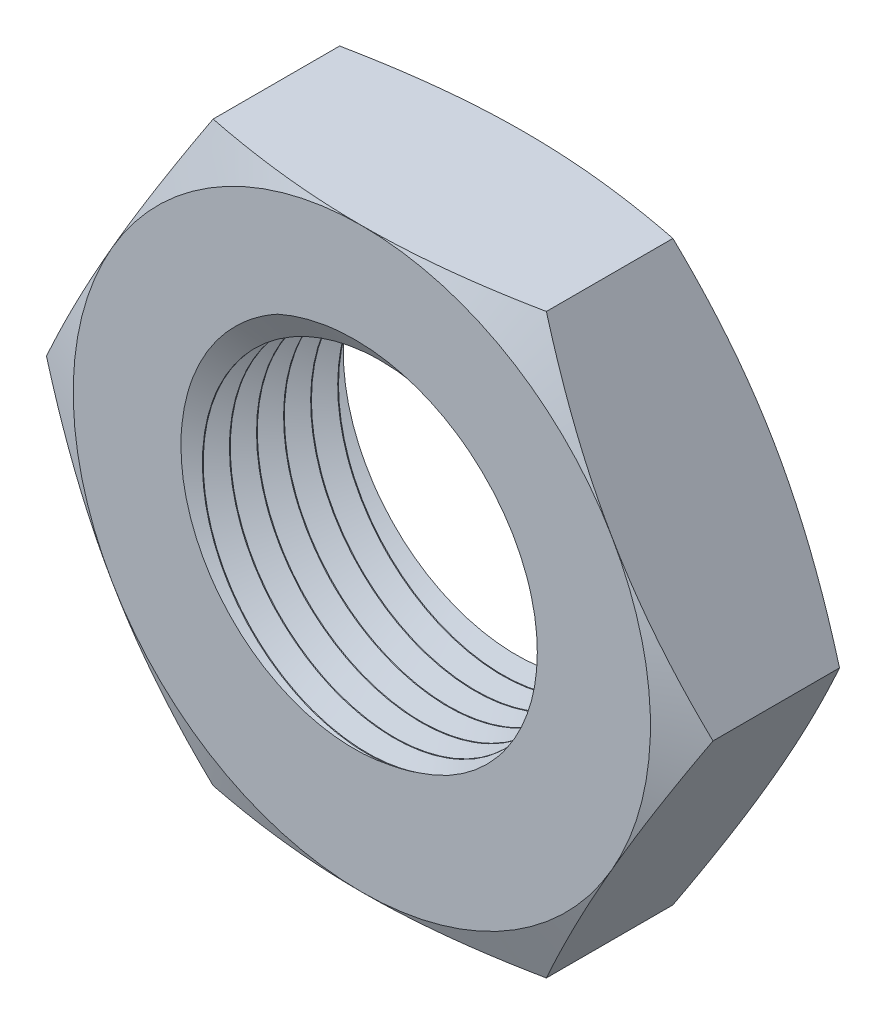
SolidWorks part; units mm, degrees
ref_plane "Alzado" through (0, 0, 0) normal (0, 0, 1) x (1, 0, 0)
ref_plane "Planta" through (0, 0, 0) normal (0, 1, 0) x (1, 0, 0)
ref_plane "Vista lateral" through (0, 0, 0) normal (1, 0, 0) x (0, 0, -1)
sketch "Croquis1" plane through (0, 0, 0) normal (0, 0, 1) x (1, 0, 0)
  line L1 (18.4752, 0) -> (9.2376, 16)
  line L2 (9.2376, 16) -> (-9.2376, 16)
  line L3 (-9.2376, 16) -> (-18.4752, 0)
  line L4 (-18.4752, 0) -> (-9.2376, -16)
  line L5 (-9.2376, -16) -> (9.2376, -16)
  line L6 (9.2376, -16) -> (18.4752, 0)
  circle A0 centre (0, 0) radius 16 construction
  circle A1 centre (0, 0) radius 9.25
  dimension "D1" = 18.5
  dimension "D2" = 32
extrude "Saliente-Extruir1" add sketch "Croquis1" along normal blind 9
sketch "Croquis2" plane through (0, 0, 0) normal (1, 0, 0) x (0, 0, -1)
  line L0 (0, 0) -> (-9, 0) construction
  line L1 (-2, 20.9886) -> (0, 20.9886)
  line L3 (0, 20.9886) -> (0, 16)
  line L4 (0, 0) -> (0, 16) construction
  line L5 (0, 16) -> (-2, 20.9886)
  line L6 (-4.5, 0) -> (-4.5, 17.953) construction
  line L7 (-9, 16) -> (-7, 20.9886)
  line L9 (-9, 20.9886) -> (-9, 16)
  line L10 (-7, 20.9886) -> (-9, 20.9886)
  dimension "D2" = 2
revolve "Cortar-Revolución2" cut sketch "Croquis2" angle 360 about L0
ref_plane "Plano1" through (0, 0, -10) normal (0, 0, -1) x (-1, 0, 0)
sketch "Croquis3" plane through (0, 0, -10) normal (0, 0, -1) x (-1, 0, 0)
  circle A0 centre (0, 0) radius 9.25 construction
  circle A1 centre (0, 0) radius 9.25
curve "Hélice/Espiral1" pitch 1.5 height 30.75 radius 9.25 centre (0, 0, -10) axis (0, 0, 1) start towards (0.7071, 0.7071, 0)
ref_plane "Plano2" through (6.5407, 6.5407, -10) normal (-0.7069, 0.7069, 0.0258) x (0.7073, 0.7064, 0.0258)
sketch "Croquis4" plane through (6.5407, 6.5407, -10) normal (-0.7069, 0.7069, 0.0258) x (0.7073, 0.7064, 0.0258)
  line L0 (-0.014, -0.0155) -> (0.0215, -1.4882)
  line L1 (0.0215, -1.4882) -> (1.2763, -0.6694)
  line L2 (1.2763, -0.6694) -> (-0.014, -0.0155)
  dimension "D1" = 60
sweep "Cortar-Barrer1" cut profiles "Croquis4" path "Hélice/Espiral1" align with end faces yes
